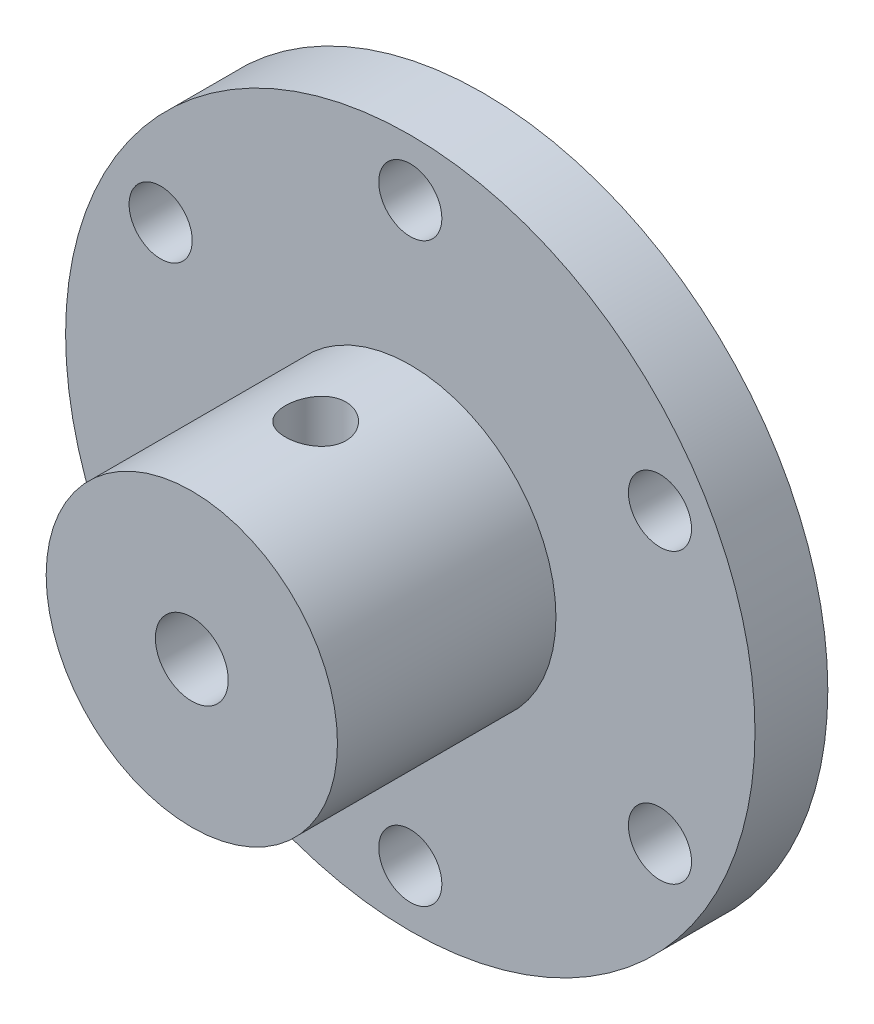
SolidWorks part; units mm, degrees
ref_plane "Front Plane" through (0, 0, 0) normal (0, 0, 1) x (1, 0, 0)
ref_plane "Top Plane" through (0, 0, 0) normal (0, 1, 0) x (1, 0, 0)
ref_plane "Right Plane" through (0, 0, 0) normal (1, 0, 0) x (0, 0, -1)
sketch "Sketch1" plane through (0, 0, 0) normal (0, 0, 1) x (1, 0, 0)
  circle A0 centre (0, 0) radius 28.4
  circle A1 centre (0, 23.75) radius 2.6
  circle A2 centre (0, 0) radius 23.75 construction
  circle A3 centre (20.5681, 11.875) radius 2.6
  circle A4 centre (20.5681, -11.875) radius 2.6
  circle A5 centre (0, -23.75) radius 2.6
  circle A6 centre (-20.5681, -11.875) radius 2.6
  circle A7 centre (-20.5681, 11.875) radius 2.6
  circle A8 centre (0, 0) radius 3
  point P19 (0, 0)
  dimension "D1" = 56.8
  dimension "D2" = 47.5
  dimension "D3" = 5.2
  dimension "D5" = 6
  dimension "D4" = 6
extrude "Boss-Extrude1" add sketch "Sketch1" along normal blind 6 contours A0 A8 A7 A6 A5 A4 A3 A1 | A8 region at (-27.5967, 0, 0) region at (0, 0, 0)
sketch "Sketch3" plane through (0, 0, 0) normal (0, 0, -1) x (-1, 0, 0)
  circle A0 centre (0, 0) radius 12
  dimension "D1" = 24
extrude "Boss-Extrude2" add sketch "Sketch3" against normal blind 24
extrude "Cut-Extrude1" cut sketch "Sketch1<3>" along normal up to surface (24 mm away) contours A8 region at (0, 0, 0) up to face at (-12, 0, 24)
sketch "Sketch1<3>" plane through (0, 0, 0) normal (0, 0, 1) x (1, 0, 0) same geometry as "Sketch1"
sketch "Sketch4" plane through (0, 0, 0) normal (0, 1, 0) x (1, 0, 0)
  line L0 (-12, -24) -> (12, -24) construction
  circle A0 centre (0, -13.8) radius 2.5
  dimension "D2" = 5
  dimension "D1" = 10.2
extrude "Cut-Extrude2" cut sketch "Sketch4" along normal up to surface (12 mm away) up to face at (12, 0, 6)
